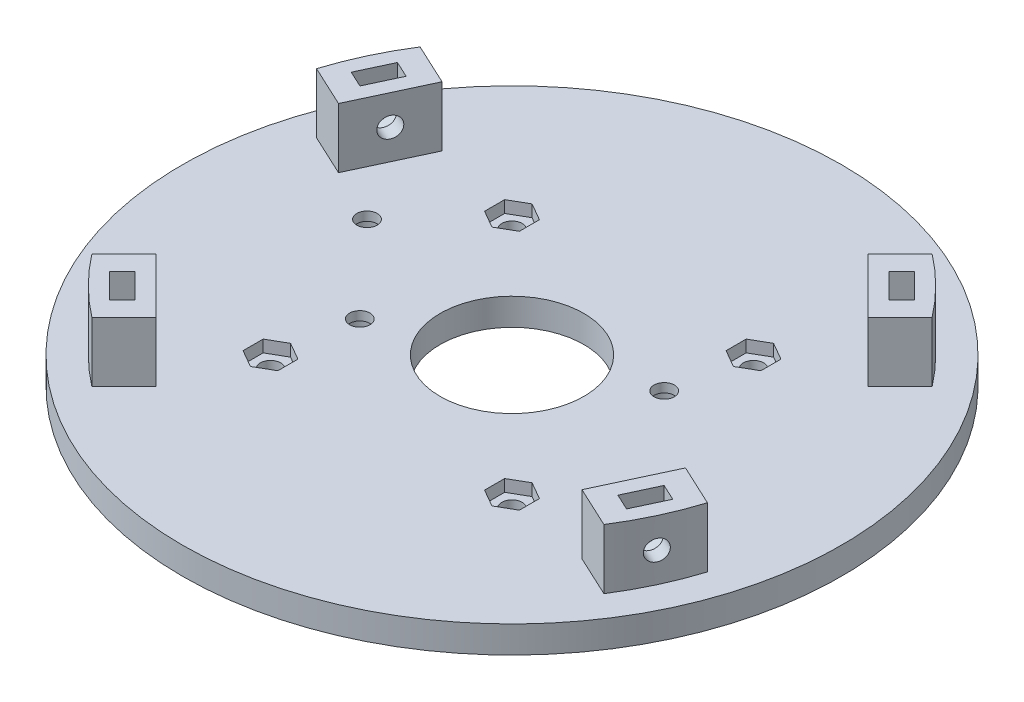
SolidWorks part; units mm, degrees
material "PLA"
ref_plane "Alzado" through (0, 0, 0) normal (0, 0, 1) x (1, 0, 0)
ref_plane "Planta" through (0, 0, 0) normal (0, 1, 0) x (1, 0, 0)
ref_plane "Vista lateral" through (0, 0, 0) normal (1, 0, 0) x (0, 0, -1)
sketch "Croquis1" plane through (0, 0, 0) normal (0, 0, 1) x (1, 0, 0)
  line L0 (0, 115.9472) -> (0, -109.96) construction
  line L2 (12, 4.5) -> (55, 4.5)
  line L3 (12, 4.5) -> (12, 0)
  line L4 (12, 0) -> (55, 0)
  line L5 (55, 4.5) -> (55, 0)
  line L6 (12, 4.5) -> (55, 0) construction
  line L7 (12, 0) -> (55, 4.5) construction
  point P3 (33.5, 2.25)
  dimension "D1" = 12
  dimension "D2" = 55
  dimension "D3" = 4.5
revolve "Revolución1" add sketch "Croquis1" angle 360 about L0
sketch "Croquis2" plane through (0, 4.5, 0) normal (0, 1, 0) x (1, 0, 0)
  line L0 (-17.9, -7.5) -> (31.7, -7.5) construction
  line L1 (20.1525, -20.1525) -> (-20.1525, -20.1525) construction
  line L2 (20.1525, -20.1525) -> (20.1525, 20.1525) construction
  line L3 (20.1525, 20.1525) -> (-20.1525, 20.1525) construction
  line L4 (-20.1525, -20.1525) -> (-20.1525, 20.1525) construction
  line L5 (20.1525, -20.1525) -> (-20.1525, 20.1525) construction
  line L6 (20.1525, 20.1525) -> (-20.1525, -20.1525) construction
  line L7 (-31.7, 7.5) -> (17.9, 7.5) construction
  circle A0 centre (0, 0) radius 28.5 construction
  circle A1 centre (-31.7, 7.5) radius 1.7
  circle A2 centre (17.9, 7.5) radius 1.7
  circle A3 centre (-17.9, -7.5) radius 1.7
  circle A4 centre (31.7, -7.5) radius 1.7
  circle A5 centre (20.1525, 20.1525) radius 1.7
  circle A6 centre (-20.1525, 20.1525) radius 1.7
  circle A7 centre (-20.1525, -20.1525) radius 1.7
  circle A8 centre (20.1525, -20.1525) radius 1.7
  circle A9 centre (0, 0) radius 55 construction
  dimension "D1" = 57
  dimension "D2" = 3.4
  dimension "D7" = 7.5
  dimension "D3" = 31.7
  dimension "D4" = 7.5
  dimension "D5" = 49.6
  dimension "D6" = 31.7
extrude "Cortar-Extruir1" cut sketch "Croquis2" against normal blind 10
sketch "Croquis3" plane through (0, 4.5, 0) normal (0, 1, 0) x (1, 0, 0)
  line L0 (0, 25.1495) -> (0, -25.1134) construction
  line L1 (-20.1525, 23.5025) -> (-23.0537, 21.8275)
  line L2 (-23.0537, 21.8275) -> (-23.0537, 18.4775)
  line L3 (-23.0537, 18.4775) -> (-20.1525, 16.8025)
  line L4 (-20.1525, 16.8025) -> (-17.2514, 18.4775)
  line L5 (-17.2514, 18.4775) -> (-17.2514, 21.8275)
  line L6 (-17.2514, 21.8275) -> (-20.1525, 23.5025)
  line L7 (20.1525, 23.5025) -> (17.2514, 21.8275)
  line L8 (17.2514, 21.8275) -> (17.2514, 18.4775)
  line L9 (17.2514, 18.4775) -> (20.1525, 16.8025)
  line L10 (20.1525, 16.8025) -> (23.0537, 18.4775)
  line L11 (23.0537, 18.4775) -> (23.0537, 21.8275)
  line L12 (23.0537, 21.8275) -> (20.1525, 23.5025)
  line L13 (-20.1525, -16.8025) -> (-23.0537, -18.4775)
  line L14 (-23.0537, -18.4775) -> (-23.0537, -21.8275)
  line L15 (-23.0537, -21.8275) -> (-20.1525, -23.5025)
  line L16 (-20.1525, -23.5025) -> (-17.2514, -21.8275)
  line L17 (-17.2514, -21.8275) -> (-17.2514, -18.4775)
  line L18 (-17.2514, -18.4775) -> (-20.1525, -16.8025)
  line L19 (20.1525, -16.8025) -> (17.2514, -18.4775)
  line L20 (17.2514, -18.4775) -> (17.2514, -21.8275)
  line L21 (17.2514, -21.8275) -> (20.1525, -23.5025)
  line L22 (20.1525, -23.5025) -> (23.0537, -21.8275)
  line L23 (23.0537, -21.8275) -> (23.0537, -18.4775)
  line L24 (23.0537, -18.4775) -> (20.1525, -16.8025)
  circle A0 centre (-20.1525, 20.1525) radius 3.35 construction
  circle A1 centre (20.1525, 20.1525) radius 3.35 construction
  circle A2 centre (-20.1525, -20.1525) radius 3.35 construction
  circle A3 centre (20.1525, -20.1525) radius 3.35 construction
  dimension "D1" = 6.7
extrude "Cortar-Extruir2" cut sketch "Croquis3" against normal blind 2
sketch "Croquis4" plane through (0, 0, 0) normal (0, 1, 0) x (1, 0, 0)
  circle A0 centre (-31.7, 7.5) radius 2.95
  circle A1 centre (-17.9, -7.5) radius 2.95
  circle A2 centre (17.9, 7.5) radius 2.95
  circle A3 centre (31.7, -7.5) radius 2.95
  dimension "D1" = 5.9
extrude "Cortar-Extruir3" cut sketch "Croquis4" along normal blind 3
sketch "Croquis5" plane through (0, 4.5, 0) normal (0, 1, 0) x (1, 0, 0)
  line L0 (0, 0) -> (0, -55) construction
  line L1 (0, 0) -> (-29.6985, -29.6985) construction
  line L2 (-34.2947, -25.1023) -> (-25.1023, -34.2947)
  line L3 (-25.1023, -34.2947) -> (-30.4591, -39.6515)
  line L5 (-34.2947, -25.1023) -> (-39.6515, -30.4591)
  circle A0 centre (0, 0) radius 55 construction
  arc A1 (-39.6515, -30.4591) -> (-30.4591, -39.6515) centre (0, 0) ccw
  point P8 (-29.6985, -29.6985)
  dimension "D4" = 100
  dimension "D1" = 45
  dimension "D2" = 42
  dimension "D3" = 13
extrude "Saliente-Extruir1" add sketch "Croquis5" along normal blind 10
sketch "Croquis6" plane through (-29.6985, 0, 29.6985) normal (0.7071, 0, -0.7071) x (-0.7071, 0, -0.7071)
  line L0 (-6.5, 14.5) -> (6.5, 14.5) construction
  circle A0 centre (0, 9.5) radius 1.7
  dimension "D2" = 3.4
  dimension "D1" = 5
extrude "Cortar-Extruir4" cut sketch "Croquis6" against normal blind 10
ref_plane "Plano1" through (-35.3553, 0, 35.3553) normal (-0.7071, 0, 0.7071) x (0.7071, 0, 0.7071)
ref_plane "Plano2" through (-32.5269, 0, 32.5269) normal (-0.7071, 0, 0.7071) x (0.7071, 0, 0.7071)
sketch "Croquis7" plane through (-32.5269, 0, 32.5269) normal (-0.7071, 0, 0.7071) x (0.7071, 0, 0.7071)
  line L0 (-2.9012, 11.175) -> (-2.9012, 17.825)
  line L1 (0, 12.85) -> (-2.9012, 11.175) construction
  line L2 (-2.9012, 11.175) -> (-2.9012, 7.825)
  line L3 (-2.9012, 7.825) -> (0, 6.15)
  line L4 (0, 6.15) -> (2.9012, 7.825)
  line L5 (2.9012, 7.825) -> (2.9012, 11.175)
  line L6 (2.9012, 11.175) -> (0, 12.85) construction
  line L7 (-2.9012, 17.825) -> (2.9012, 17.825)
  line L8 (2.9012, 17.825) -> (2.9012, 11.175)
  line L9 (-6.5, 14.5) -> (-6.5, 4.5) construction
  circle A0 centre (0, 9.5) radius 3.35 construction
  dimension "D2" = 6.7
  dimension "D1" = 10
extrude "Cortar-Extruir5" cut sketch "Croquis7" against normal blind 1.5 and the other way blind 1.5
pattern_circular "MatrizC1" count 2 over 70 about axis through (0, 115.9472, 0) along (0, 1, 0) of "Saliente-Extruir1", "Cortar-Extruir4", "Cortar-Extruir5" reverse direction yes
pattern_circular "MatrizC2" count 2 over 360 about axis through (0, 4.5, 0) along (0, 1, 0) of "MatrizC1"
